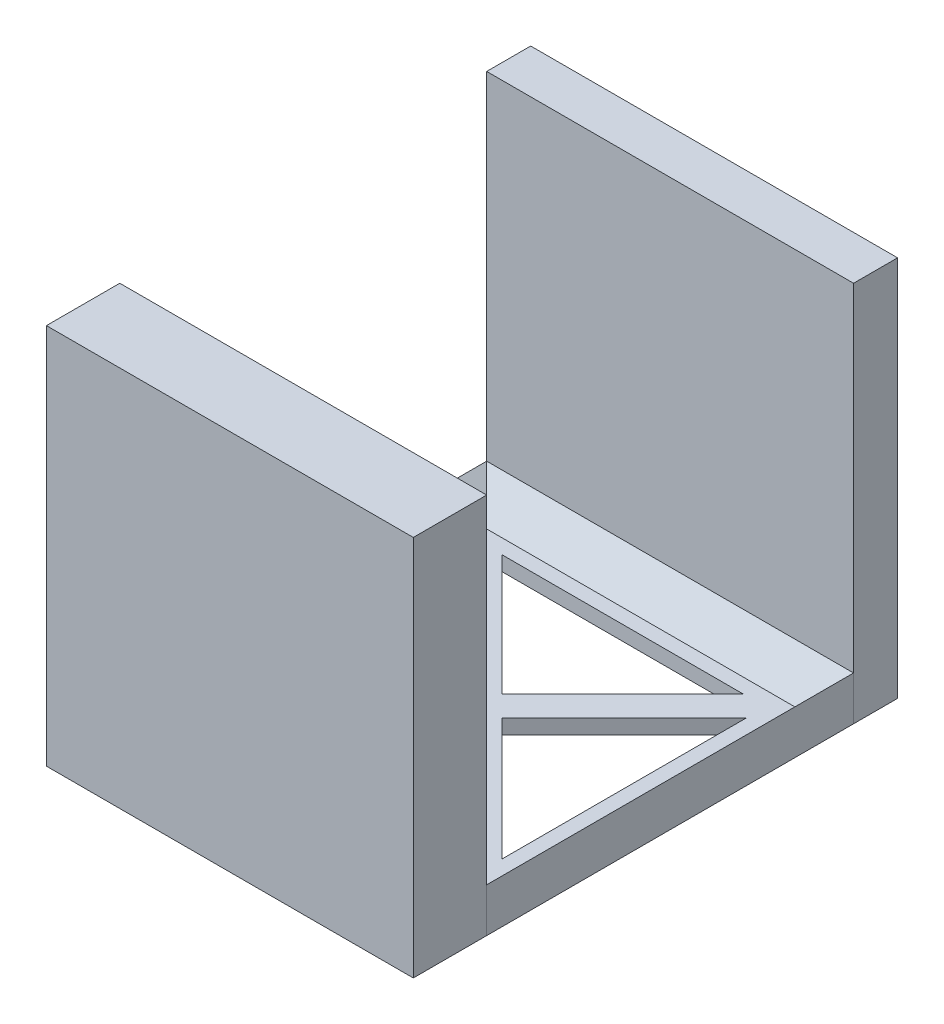
SolidWorks part; units mm, degrees
ref_plane "Ebene vorne" through (0, 0, 0) normal (0, 0, 1) x (1, 0, 0)
ref_plane "Ebene oben" through (0, 0, 0) normal (0, 1, 0) x (1, 0, 0)
ref_plane "Ebene rechts" through (0, 0, 0) normal (1, 0, 0) x (0, 0, -1)
sketch "Skizze1" plane through (0, 0, 0) normal (0, 1, 0) x (1, 0, 0)
  line L4 (82.5119, -11.5657) -> (82.5119, 13.4343)
  line L8 (82.5119, 13.4343) -> (82.5119, -11.5657)
  line L9 (82.5119, 13.4343) -> (57.5119, 13.4343)
  line L10 (82.5119, 13.4343) -> (82.5119, -11.5657)
  line L11 (82.5119, -11.5657) -> (57.5119, -11.5657)
  line L12 (57.5119, 13.4343) -> (57.5119, -11.5657)
  line L13 (77.9776, 10.4343) -> (61.5705, 10.4343)
  line L14 (79.5119, 9.1401) -> (79.5119, -7.5072)
  line L15 (77.742, -8.5657) -> (61.806, -8.5657)
  line L16 (60.5119, 8.6644) -> (60.5119, -7.0315)
  line L18 (60.5119, 8.6644) -> (68.3598, 0.8165)
  line L21 (61.5705, 10.4343) -> (69.774, 2.2307)
  line L22 (71.1883, 0.8165) -> (79.5119, -7.5072)
  line L24 (61.806, -8.5657) -> (69.774, -0.5977)
  line L27 (60.5119, -7.0315) -> (68.3598, 0.8165)
  line L30 (69.774, -0.5977) -> (77.742, -8.5657)
  line L32 (69.774, 2.2307) -> (77.9776, 10.4343)
  line L36 (71.1883, 0.8165) -> (79.5119, 9.1401)
  point P0 (0, 0)
  point P11 (69.8341, 0.7564)
  point P12 (69.9519, 0.9943)
  dimension "D1" = 25
  dimension "D2" = 3
  dimension "D3" = 3
  dimension "D4" = 3
  dimension "D5" = 3
  dimension "D7" = 2
  dimension "D8" = 2
extrude "Aufsatz-Linear austragen1" add sketch "Skizze1" along normal blind 1 contours L9 L12 L11 L4 L32 L21 L13 L27 L16 L18 L24 L30 L15 L22 L36 L14 region at (69.982, 0, -0.9195)
sketch "Skizze2" plane through (0, 1, 0) normal (0, 1, 0) x (1, 0, 0)
  line L0 (59.5119, 11.4343) -> (59.5119, -9.5657)
  line L1 (57.5119, 13.4343) -> (82.5119, 13.4343)
  line L2 (57.5119, 13.4343) -> (57.5119, -11.5657)
  line L3 (57.5119, -11.5657) -> (82.5119, -11.5657)
  line L4 (82.5119, 13.4343) -> (82.5119, -11.5657)
  line L5 (59.5119, -9.5657) -> (80.5119, -9.5657)
  line L6 (80.5119, 11.4343) -> (80.5119, -9.5657)
  line L7 (59.5119, 11.4343) -> (80.5119, 11.4343)
  dimension "D1" = 2
extrude "Aufsatz-Linear austragen2" add sketch "Skizze2" along normal blind 2
chamfer "Fase1" distance 2 angle 45 4 edges at (70.0119, 3, 9.5657) (80.5119, 3, -0.9343) (59.5119, 3, -0.9343) (70.0119, 3, -11.4343)
sketch "Skizze3" plane through (0, 0, 0) normal (0, 1, 0) x (1, 0, 0)
  line L0 (57.5119, 13.4343) -> (57.5119, -11.5657) construction
  line L1 (82.5119, -11.5657) -> (57.5119, -11.5657)
  line L2 (82.5119, -11.5657) -> (82.5119, -16.5657)
  line L3 (82.5119, -16.5657) -> (57.5119, -16.5657)
  line L4 (57.5119, -11.5657) -> (57.5119, -16.5657)
  line L6 (57.5119, 13.4343) -> (82.5119, 13.4343)
  line L7 (57.5119, 13.4343) -> (57.5119, 16.4343)
  line L8 (57.5119, 16.4343) -> (82.5119, 16.4343)
  line L9 (82.5119, 13.4343) -> (82.5119, 16.4343)
  dimension "D1" = 0
  dimension "D2" = 5
  dimension "D3" = 3
extrude "Aufsatz-Linear austragen3" add sketch "Skizze3" along normal blind 26 separate body
shell "Wandung1" thickness 1.5 removed face at (70.0119, 0, 14.0657)
sketch "Skizze4" plane through (0, 0, 11.5657) normal (0, 0, -1) x (-1, 0, 0)
  line L0 (-57.5119, 26) -> (-57.5119, 0) construction
  line L1 (-59.5119, 1) -> (-80.5119, 1) construction
  circle A0 centre (-62.5119, 16) radius 0.8
  circle A1 centre (-67.5119, 16) radius 0.8
  circle A2 centre (-72.5119, 16) radius 0.8
  circle A3 centre (-77.5119, 16) radius 0.8
  dimension "D3" = 1.6
  dimension "D1" = 5
  dimension "D2" = 15
  dimension "D4" = 4
extrude "Schnitt-Linear austragen1" cut sketch "Skizze4" against normal up to next (1.5 mm away)
